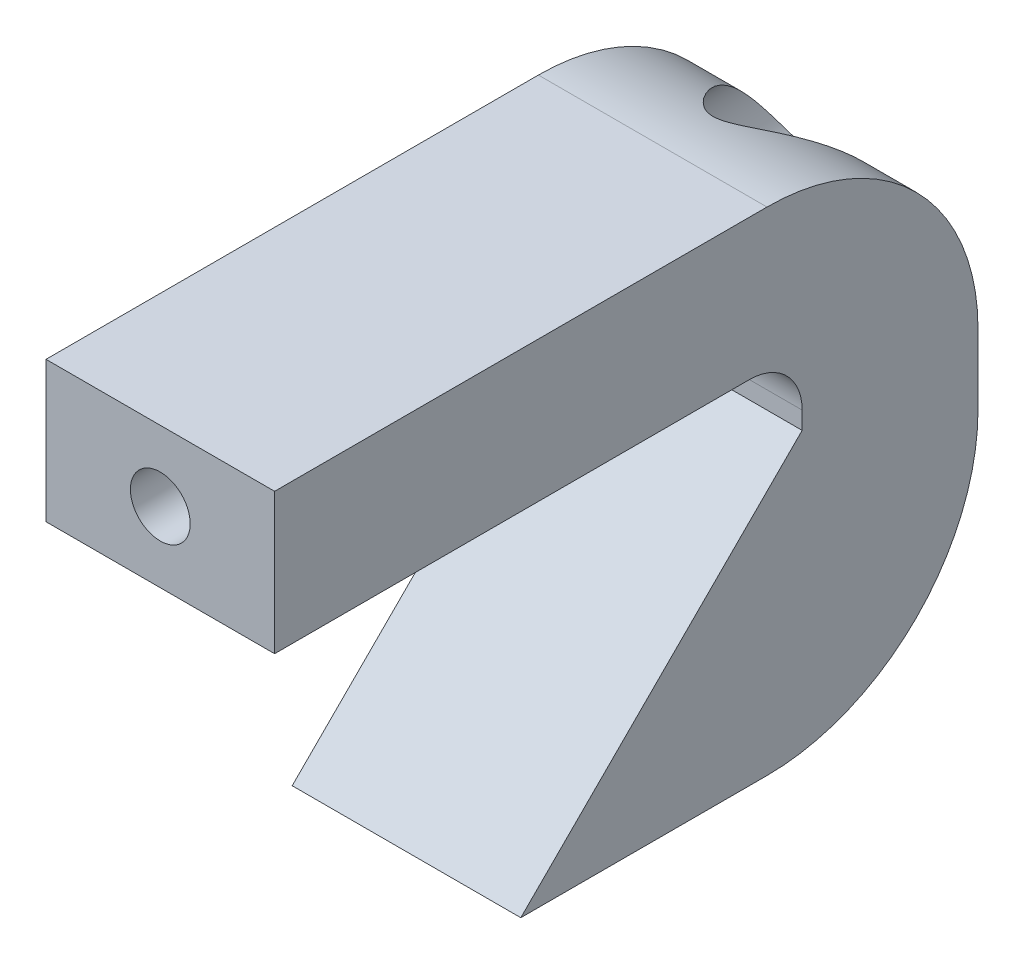
SolidWorks part; units mm, degrees
ref_plane "Płaszczyzna przednia" through (0, 0, 0) normal (0, 0, 1) x (1, 0, 0)
ref_plane "Płaszczyzna górna" through (0, 0, 0) normal (0, 1, 0) x (1, 0, 0)
ref_plane "Płaszczyzna prawa" through (0, 0, 0) normal (1, 0, 0) x (0, 0, -1)
sketch "Sketch1" plane through (0, 0, 0) normal (1, 0, 0) x (0, 0, -1)
  line L1 (0, -16) -> (-16, -16)
  line L2 (-16, -16) -> (0, 0)
  line L3 (0, -16) -> (10, -16)
  line L4 (10, -16) -> (10, 12)
  line L5 (10, 12) -> (-30, 12)
  line L6 (-30, 12) -> (-30, 4)
  line L7 (-30, 4) -> (0, 4)
  line L8 (0, 4) -> (0, 0)
  dimension "D1" = 16
  dimension "D2" = 16
  dimension "D3" = 10
  dimension "D4" = 28
  dimension "D5" = 40
  dimension "D6" = 8
  dimension "D7" = 30
extrude "Boss-Extrude1" add sketch "Sketch1" along normal blind 13
fillet "Fillet2" radius 12 2 edges at (6.5, 12, -10) (6.5, -16, -10)
fillet "Fillet4" radius 3 1 edges at (6.5, 4, 0)
sketch "Sketch2" plane through (0, 0, -10) normal (0, 0, -1) x (-1, 0, 0)
  line L1 (-13, 12) -> (0, 12) construction
  line L2 (-13, 12) -> (-13, 4) construction
  line L3 (-13, 4) -> (0, 4) construction
  line L4 (0, 12) -> (0, 4) construction
  line L5 (-13, 12) -> (0, 4) construction
  line L6 (-13, 4) -> (0, 12) construction
  circle A0 centre (-6.5, 8) radius 1.7
  point P4 (-6.5, 8)
  dimension "D1" = 13
  dimension "D2" = 8
extrude "Cut-Extrude1" cut sketch "Sketch2" against normal blind 41
sketch "Sketch3" plane through (0, 0, -10) normal (0, 0, -1) x (-1, 0, 0)
  circle A0 centre (-6.5, 8) radius 3.5
extrude "Cut-Extrude2" cut sketch "Sketch3" against normal blind 34
sketch "Sketch6" plane through (0, 0, 24) normal (0, 0, -1) x (-1, 0, 0)
  point P0 (-6.5, 8.0176)
hole_wizard "CSK for M3 Countersunk Flat Head Screw1" positions "Sketch6" profile "Sketch5" countersink size "M3" standard "ISO" end condition through all
sketch "Sketch5" plane through (6.5, 8.0176, 24) normal (1, 0, 0) x (0, 1, 0)
  line L0 (0, 0) -> (0, 6)
  line L1 (0, 6) -> (1.6, 6)
  line L2 (1.6, 6) -> (1.6, 1.55)
  line L3 (1.6, 1.55) -> (3.15, 0)
  line L5 (3.15, 0) -> (0, 0)
  line L6 (-1.6, 1.55) -> (-3.15, 0) construction
  line L11 (0, -6.35) -> (0, 107.95) construction
  dimension "Thru Hole Dia." = 3.2
  dimension "Thru Hole Depth" = 6
  dimension "Near C'Sink Dia." = 6.3
  dimension "Near C'Sink Angle" = 90
